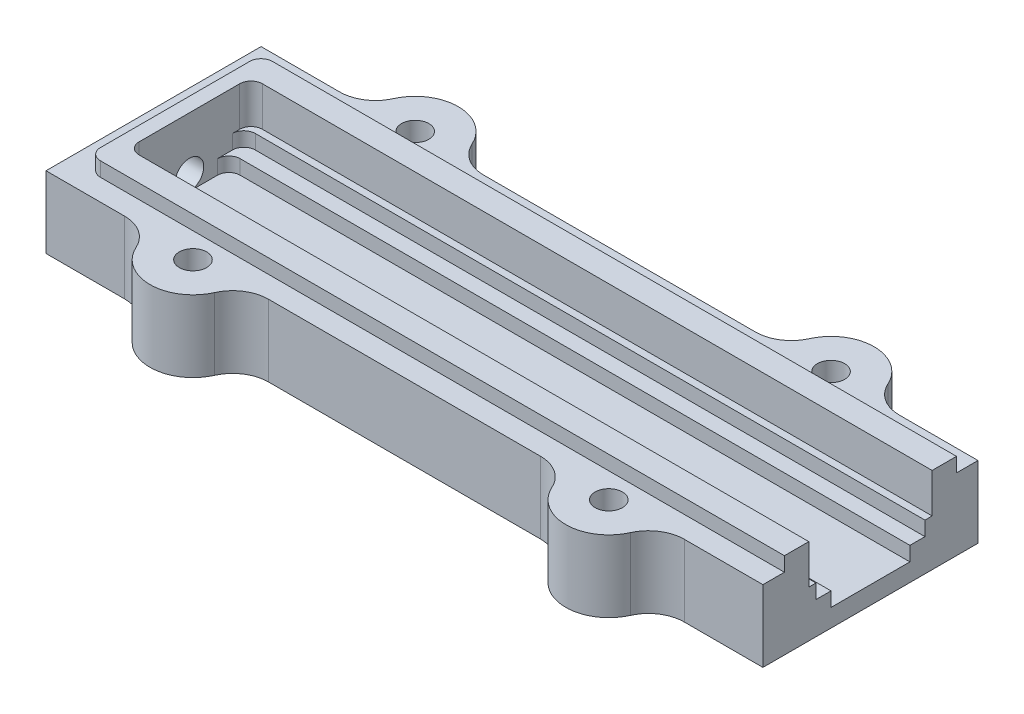
SolidWorks part; units mm, degrees
ref_plane "Front Plane" through (0, 0, 0) normal (0, 0, 1) x (1, 0, 0)
ref_plane "Top Plane" through (0, 0, 0) normal (0, 1, 0) x (1, 0, 0)
ref_plane "Right Plane" through (0, 0, 0) normal (1, 0, 0) x (0, 0, -1)
sketch "Sketch1" plane through (0, 0, 0) normal (0, 1, 0) x (1, 0, 0)
  line L1 (0, 15) -> (100, 15)
  line L2 (0, 15) -> (0, -15)
  line L3 (0, -15) -> (100, -15)
  line L4 (100, 15) -> (100, -15)
  point P4 (0, 0)
  dimension "D1" = 30
  dimension "D2" = 100
extrude "Boss-Extrude1" add sketch "Sketch1" along normal blind 20
sketch "Sketch2" plane through (0, 0, 0) normal (-1, 0, 0) x (0, 0, 1)
  line L0 (-15, 0) -> (15, 0) construction
  line L1 (-7.6, 25.5) -> (7.6, 25.5)
  line L2 (-7.6, 25.5) -> (-7.6, 10)
  line L3 (-7.6, 10) -> (7.6, 10)
  line L4 (7.6, 25.5) -> (7.6, 10)
  point P4 (0, 10)
  dimension "D1" = 15.2
  dimension "D2" = 15.5
  dimension "D3" = 10
extrude "Cut-Extrude1" cut sketch "Sketch2" against normal through all
sketch "Sketch3" plane through (0, 0, 0) normal (-1, 0, 0) x (0, 0, 1)
  line L0 (-7.6, 10) -> (7.6, 10) construction
  line L1 (-5.5, 10) -> (5.5, 10)
  line L2 (-5.5, 10) -> (-5.5, 8)
  line L3 (-5.5, 8) -> (5.5, 8)
  line L4 (5.5, 10) -> (5.5, 8)
  point P6 (0, 8)
  dimension "D1" = 2
  dimension "D2" = 11
extrude "Cut-Extrude2" cut sketch "Sketch3" against normal through all
sketch "Sketch4" plane through (0, 0, 0) normal (-1, 0, 0) x (0, 0, 1)
  line L0 (7.6, 10) -> (7.6, 20) construction
  line L1 (7.6, 12) -> (8.6, 12)
  line L2 (7.6, 12) -> (7.6, 20)
  line L3 (7.6, 20) -> (8.6, 20)
  line L4 (8.6, 12) -> (8.6, 20)
  line L5 (7.6, 20) -> (15, 20) construction
  line L6 (-7.6, 20) -> (-7.6, 10) construction
  line L7 (-7.6, 12) -> (-8.6, 12)
  line L8 (-7.6, 12) -> (-7.6, 20)
  line L9 (-7.6, 20) -> (-8.6, 20)
  line L10 (-8.6, 12) -> (-8.6, 20)
  line L11 (-15, 20) -> (-7.6, 20) construction
  line L12 (5.5, 10) -> (7.6, 10) construction
  point P16 (6.55, 10)
  dimension "D1" = 2
  dimension "D2" = 1
  dimension "D3" = 1
extrude "Cut-Extrude3" cut sketch "Sketch4" against normal through all
sketch "Sketch5" plane through (100, 0, 0) normal (1, 0, 0) x (0, 0, -1)
  line L0 (7.6, 10) -> (5.5, 10) construction
  line L1 (-12, 17.5) -> (12, 17.5)
  line L2 (-15, 17.5) -> (-15, 20)
  line L3 (-15, 20) -> (15, 20)
  line L4 (15, 17.5) -> (15, 20)
  line L5 (-15, 20) -> (-15, 0) construction
  line L6 (15, 20) -> (15, 0) construction
  line L7 (8.6, 20) -> (15, 20) construction
  line L10 (12, 17.5) -> (12, 15.5)
  line L11 (12, 15.5) -> (15, 15.5)
  line L12 (15, 17.5) -> (15, 15.5)
  line L13 (-15, 17.5) -> (-15, 15.5)
  line L14 (-15, 15.5) -> (-12, 15.5)
  line L15 (-12, 17.5) -> (-12, 15.5)
  dimension "D1" = 7.5
  dimension "D2" = 3
  dimension "D3" = 3
  dimension "D4" = 2
  dimension "D5" = 2
extrude "Cut-Extrude4" cut sketch "Sketch5" against normal through all
sketch "Sketch6" plane through (0, 17.5, 0) normal (0, 1, 0) x (1, 0, 0)
  line L0 (0, -8.6) -> (100, -8.6) construction
  line L1 (0, 8.6) -> (5, 8.6)
  line L2 (0, 8.6) -> (0, -8.6)
  line L3 (0, -8.6) -> (5, -8.6)
  line L4 (5, 8.6) -> (5, -8.6)
  dimension "D1" = 5
extrude "Boss-Extrude2" add sketch "Sketch6" against normal up to next
fillet "Fillet1" radius 1.5875 4 edges at (5, 9, 5.5) (5, 14.75, 8.6) (5, 9, -5.5) (5, 14.75, -8.6)
fillet "Fillet2" radius 1.5875 2 edges at (5.1127, 11, 7.6) (5.1127, 11, -7.6)
sketch "Sketch7" plane through (0, 17.5, 0) normal (0, 1, 0) x (1, 0, 0)
  line L0 (0, 12) -> (100, 12) construction
  line L1 (0, -12) -> (3, -12)
  line L2 (0, -12) -> (0, 12)
  line L3 (0, 12) -> (3, 12)
  line L4 (3, -12) -> (3, 12)
  dimension "D1" = 3
extrude "Cut-Extrude5" cut sketch "Sketch7" against normal up to surface (2 mm away) up to face at (50, 15.5, -13.5)
fillet "Fillet3" radius 1.5875 2 edges at (3, 16.5, 12) (3, 16.5, -12)
sketch "Sketch8" plane through (0, 0, 0) normal (0, -1, 0) x (1, 0, 0)
  line L0 (15, 15) -> (15, 15.5)
  line L1 (0, 15) -> (100, 15) construction
  line L2 (27, 15.5) -> (27, 15)
  line L3 (27, 15) -> (15, 15)
  line L4 (73, 15) -> (73, 15.5)
  line L5 (85, 15.5) -> (85, 15)
  line L6 (85, 15) -> (73, 15)
  line L7 (0, -15) -> (0, 15) construction
  line L8 (100, 15) -> (100, -15) construction
  arc A0 (15, 15.5) -> (27, 15.5) centre (21, 15.5) cw
  arc A1 (73, 15.5) -> (85, 15.5) centre (79, 15.5) cw
  dimension "D1" = 15
  dimension "D2" = 15
  dimension "D3" = 12
  dimension "D4" = 12
  dimension "D5" = 0.5
extrude "Boss-Extrude3" add sketch "Sketch8" against normal up to surface (15.5 mm away) up to face at (41.4517, 15.5, 0)
mirror "Mirror1" about plane through (0, 0, 0) normal (0, 0, 1) of "Boss-Extrude3"
sketch "Sketch9" plane through (0, 15.5, 0) normal (0, 1, 0) x (1, 0, 0)
  circle A0 centre (21, 15.5) radius 1.905
  circle A1 centre (79, 15.5) radius 1.905
  circle A2 centre (79, -15.5) radius 1.905
  circle A3 centre (21, -15.5) radius 1.905
  dimension "D1" = 3.81
extrude "Cut-Extrude6" cut sketch "Sketch9" against normal through all
fillet "Fillet4" radius 5 8 edges at (73, 7.75, 15) (85, 7.75, 15) (85, 7.75, -15) (73, 7.75, -15)
sketch "Sketch10" plane through (5, 0, 0) normal (1, 0, 0) x (0, 0, -1)
  line L0 (5.5, 8) -> (-5.5, 8) construction
  circle A0 centre (0, 10) radius 2
  dimension "D1" = 4
extrude "Cut-Extrude7" cut sketch "Sketch10" against normal through all
sketch "Sketch15" plane through (100, 0, 0) normal (1, 0, 0) x (0, 0, -1)
  line L0 (8.6, 17.5) -> (12, 17.5) construction
  line L1 (-26.2969, 5.5) -> (26.8311, 5.5)
  line L2 (-26.2969, 5.5) -> (-26.2969, -0.4361)
  line L3 (-26.2969, -0.4361) -> (26.8311, -0.4361)
  line L4 (26.8311, 5.5) -> (26.8311, -0.4361)
  dimension "D1" = 12
extrude "Cut-Extrude8" cut sketch "Sketch15" against normal through all
sketch "Sketch11" plane through (0, 5.5, 0) normal (0, 1, 0) x (1, 0, 0)
  line L0 (100, 12) -> (100, 15) construction
  line L1 (-10, 55.5) -> (100, 55.5)
  line L2 (-10, 55.5) -> (-10, -21.5)
  line L3 (-10, -21.5) -> (100, -21.5)
  line L4 (100, 55.5) -> (100, -21.5)
  line L5 (68.9626, 15) -> (31.0374, 15) construction
  line L6 (10.9626, 15) -> (0, 15) construction
  arc A0 (73.525, -17.9545) -> (84.475, -17.9545) centre (79, -15.5) ccw construction
  dimension "D1" = 77
  dimension "D2" = 110
  dimension "D3" = 40.5
  dimension "D4" = 36.5
sketch "Sketch12" plane through (0, 12, 0) normal (0, 1, 0) x (1, 0, 0)
  line L0 (100, 7.6) -> (6.5875, 7.6) construction
  line L1 (100, -7.6) -> (6.5875, -7.6) construction
  line L2 (100, 7.6) -> (6.5875, 7.6)
  line L3 (100, -7.6) -> (6.5875, -7.6)
  line L4 (5, -6.0125) -> (5, 6.0125)
  arc A0 (6.5875, 7.6) -> (5, 6.0125) centre (6.5875, 6.0125) ccw construction
  arc A1 (5, -6.0125) -> (6.5875, -7.6) centre (6.5875, -6.0125) ccw construction
  arc A2 (6.5875, 7.6) -> (5, 6.0125) centre (6.5875, 6.0125) ccw
  arc A3 (5, -6.0125) -> (6.5875, -7.6) centre (6.5875, -6.0125) ccw
sketch "Sketch13" plane through (0, 10, 0) normal (0, 1, 0) x (1, 0, 0)
  line L0 (100, 5.5) -> (6.5875, 5.5) construction
  line L1 (100, -5.5) -> (6.5875, -5.5) construction
  line L2 (100, 5.5) -> (6.5875, 5.5)
  line L3 (100, -5.5) -> (6.5875, -5.5)
  line L4 (5, -3.9125) -> (5, 3.9125)
  arc A0 (6.5875, 5.5) -> (5, 3.9125) centre (6.5875, 3.9125) ccw construction
  arc A1 (5, -3.9125) -> (6.5875, -5.5) centre (6.5875, -3.9125) ccw construction
  arc A2 (6.5875, 5.5) -> (5, 3.9125) centre (6.5875, 3.9125) ccw
  arc A3 (5, -3.9125) -> (6.5875, -5.5) centre (6.5875, -3.9125) ccw
sketch "Sketch14" plane through (0, 15.5, 0) normal (0, 1, 0) x (1, 0, 0)
  line L15 (100, 12) -> (100, 15)
  line L16 (100, 15) -> (89.0374, 15)
  line L17 (68.9626, 15) -> (31.0374, 15)
  line L18 (10.9626, 15) -> (0, 15)
  line L19 (0, 15) -> (0, -15)
  line L20 (0, -15) -> (10.9626, -15)
  line L21 (31.0374, -15) -> (68.9626, -15)
  line L22 (89.0374, -15) -> (100, -15)
  line L23 (100, -15) -> (100, -12)
  line L24 (100, -12) -> (4.5875, -12)
  line L25 (3, -10.4125) -> (3, 10.4125)
  line L26 (4.5875, 12) -> (100, 12)
  line L27 (100, 12) -> (100, 15)
  line L28 (100, 15) -> (89.0374, 15)
  line L29 (68.9626, 15) -> (31.0374, 15)
  line L30 (10.9626, 15) -> (0, 15)
  line L31 (0, 15) -> (0, -15)
  line L32 (0, -15) -> (10.9626, -15)
  line L33 (31.0374, -15) -> (68.9626, -15)
  line L34 (89.0374, -15) -> (100, -15)
  line L35 (100, -15) -> (100, -12)
  line L36 (100, -12) -> (4.5875, -12)
  line L37 (3, -10.4125) -> (3, 10.4125)
  line L38 (4.5875, 12) -> (100, 12)
  arc A16 (84.475, 17.9545) -> (89.0374, 15) centre (89.0374, 20) ccw
  arc A17 (84.475, 17.9545) -> (73.525, 17.9545) centre (79, 15.5) ccw
  arc A18 (68.9626, 15) -> (73.525, 17.9545) centre (68.9626, 20) ccw
  arc A19 (26.475, 17.9545) -> (31.0374, 15) centre (31.0374, 20) ccw
  arc A20 (26.475, 17.9545) -> (15.525, 17.9545) centre (21, 15.5) ccw
  arc A21 (10.9626, 15) -> (15.525, 17.9545) centre (10.9626, 20) ccw
  arc A22 (15.525, -17.9545) -> (10.9626, -15) centre (10.9626, -20) ccw
  arc A23 (15.525, -17.9545) -> (26.475, -17.9545) centre (21, -15.5) ccw
  arc A24 (31.0374, -15) -> (26.475, -17.9545) centre (31.0374, -20) ccw
  arc A25 (73.525, -17.9545) -> (68.9626, -15) centre (68.9626, -20) ccw
  arc A26 (73.525, -17.9545) -> (84.475, -17.9545) centre (79, -15.5) ccw
  arc A27 (89.0374, -15) -> (84.475, -17.9545) centre (89.0374, -20) ccw
  arc A28 (3, -10.4125) -> (4.5875, -12) centre (4.5875, -10.4125) ccw
  arc A29 (4.5875, 12) -> (3, 10.4125) centre (4.5875, 10.4125) ccw
  arc A30 (84.475, 17.9545) -> (89.0374, 15) centre (89.0374, 20) ccw
  arc A31 (84.475, 17.9545) -> (73.525, 17.9545) centre (79, 15.5) ccw
  arc A32 (68.9626, 15) -> (73.525, 17.9545) centre (68.9626, 20) ccw
  arc A33 (26.475, 17.9545) -> (31.0374, 15) centre (31.0374, 20) ccw
  arc A34 (26.475, 17.9545) -> (15.525, 17.9545) centre (21, 15.5) ccw
  arc A35 (10.9626, 15) -> (15.525, 17.9545) centre (10.9626, 20) ccw
  arc A36 (15.525, -17.9545) -> (10.9626, -15) centre (10.9626, -20) ccw
  arc A37 (15.525, -17.9545) -> (26.475, -17.9545) centre (21, -15.5) ccw
  arc A38 (31.0374, -15) -> (26.475, -17.9545) centre (31.0374, -20) ccw
  arc A39 (73.525, -17.9545) -> (68.9626, -15) centre (68.9626, -20) ccw
  arc A40 (73.525, -17.9545) -> (84.475, -17.9545) centre (79, -15.5) ccw
  arc A41 (89.0374, -15) -> (84.475, -17.9545) centre (89.0374, -20) ccw
  arc A42 (3, -10.4125) -> (4.5875, -12) centre (4.5875, -10.4125) ccw
  arc A43 (4.5875, 12) -> (3, 10.4125) centre (4.5875, 10.4125) ccw
  dimension "D1" = 0
sketch "Sketch16" plane through (0, 17.5, 0) normal (0, 1, 0) x (1, 0, 0)
  line L0 (100, -12) -> (100, -8.6) construction
  line L1 (100, -21.5) -> (0, -21.5)
  line L2 (100, -21.5) -> (100, 25.5)
  line L3 (100, 25.5) -> (0, 25.5)
  line L4 (0, -21.5) -> (0, 25.5)
  line L5 (0, -15) -> (0, 15) construction
  arc A0 (15.525, -17.9545) -> (26.475, -17.9545) centre (21, -15.5) ccw construction
  arc A2 (26.475, 17.9545) -> (15.525, 17.9545) centre (21, 15.5) ccw construction
  dimension "D1" = 10
sketch "Sketch17" plane through (0, 5.5, 0) normal (0, -1, 0) x (1, 0, 0)
  line L0 (42.4984, 15) -> (31.0374, 15)
  line L1 (42.4984, 15) -> (50.4984, 15)
  line L2 (100, 4.6395) -> (100, -3.3605)
  line L3 (50.8125, -15) -> (68.9626, -15)
  line L4 (10.9626, -15) -> (0, -15) construction
  line L5 (0, -2.9059) -> (0, -15)
  line L6 (100, 4.6395) -> (100, 15)
  line L7 (98.8337, -15) -> (100, -15)
  line L8 (0, 15) -> (0, -15)
  line L9 (0, -15) -> (10.9626, -15)
  line L10 (31.0374, -15) -> (68.9626, -15)
  line L11 (89.0374, -15) -> (100, -15)
  line L12 (100, -15) -> (100, 15)
  line L13 (100, 15) -> (89.0374, 15)
  line L14 (68.9626, 15) -> (31.0374, 15)
  line L15 (10.9626, 15) -> (0, 15)
  line L16 (0, 15) -> (0, 5.0941)
  line L17 (0, -15) -> (2.2465, -15)
  line L18 (31.0374, -15) -> (42.8125, -15)
  line L19 (89.0374, -15) -> (90.8337, -15)
  line L20 (100, -15) -> (100, -3.3605)
  line L21 (100, 15) -> (89.0374, 15)
  line L22 (68.9626, 15) -> (50.4984, 15)
  line L23 (10.9626, 15) -> (0, 15)
  line L24 (100, -15) -> (89.0374, -15) construction
  line L25 (10.2465, -15) -> (10.9626, -15)
  arc A12 (15.525, -17.9545) -> (10.9626, -15) centre (10.9626, -20) ccw
  arc A13 (15.525, -17.9545) -> (26.475, -17.9545) centre (21, -15.5) ccw
  arc A14 (31.0374, -15) -> (26.475, -17.9545) centre (31.0374, -20) ccw
  arc A15 (73.525, -17.9545) -> (68.9626, -15) centre (68.9626, -20) ccw
  arc A16 (73.525, -17.9545) -> (84.475, -17.9545) centre (79, -15.5) ccw
  arc A17 (89.0374, -15) -> (84.475, -17.9545) centre (89.0374, -20) ccw
  arc A18 (84.475, 17.9545) -> (89.0374, 15) centre (89.0374, 20) ccw
  arc A19 (84.475, 17.9545) -> (73.525, 17.9545) centre (79, 15.5) ccw
  arc A20 (68.9626, 15) -> (73.525, 17.9545) centre (68.9626, 20) ccw
  arc A21 (26.475, 17.9545) -> (31.0374, 15) centre (31.0374, 20) ccw
  arc A22 (26.475, 17.9545) -> (15.525, 17.9545) centre (21, 15.5) ccw
  arc A23 (10.9626, 15) -> (15.525, 17.9545) centre (10.9626, 20) ccw
  arc A24 (15.525, -17.9545) -> (10.9626, -15) centre (10.9626, -20) ccw
  arc A25 (15.525, -17.9545) -> (26.475, -17.9545) centre (21, -15.5) ccw
  arc A26 (31.0374, -15) -> (26.475, -17.9545) centre (31.0374, -20) ccw
  arc A27 (73.525, -17.9545) -> (68.9626, -15) centre (68.9626, -20) ccw
  arc A28 (73.525, -17.9545) -> (84.475, -17.9545) centre (79, -15.5) ccw
  arc A29 (89.0374, -15) -> (84.475, -17.9545) centre (89.0374, -20) ccw
  arc A30 (84.475, 17.9545) -> (89.0374, 15) centre (89.0374, 20) ccw
  arc A31 (84.475, 17.9545) -> (73.525, 17.9545) centre (79, 15.5) ccw
  arc A32 (68.9626, 15) -> (73.525, 17.9545) centre (68.9626, 20) ccw
  arc A33 (26.475, 17.9545) -> (31.0374, 15) centre (31.0374, 20) ccw
  arc A34 (26.475, 17.9545) -> (15.525, 17.9545) centre (21, 15.5) ccw
  arc A35 (10.9626, 15) -> (15.525, 17.9545) centre (10.9626, 20) ccw
  dimension "D2" = 8
  dimension "D3" = 8
  dimension "D4" = 8
  dimension "D5" = 8
  dimension "D6" = 8
  dimension "D7" = 8
  dimension "D1" = 0
